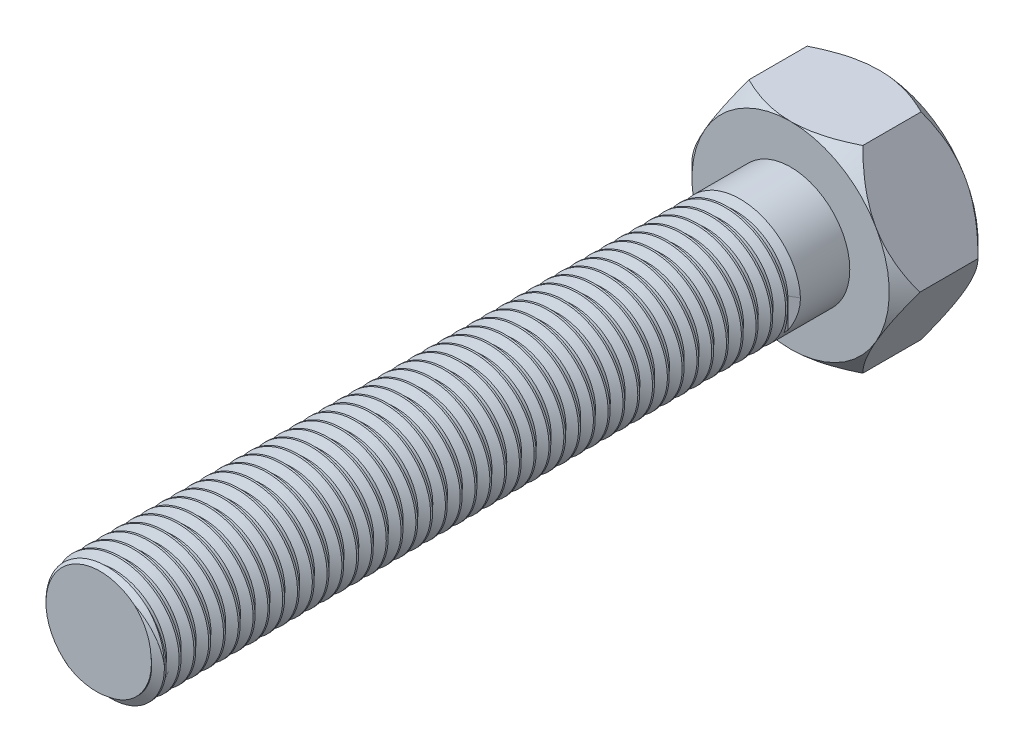
SolidWorks part; units mm, degrees
ref_plane "Front Plane" through (0, 0, 0) normal (0, 0, 1) x (1, 0, 0)
ref_plane "Top Plane" through (0, 0, 0) normal (0, 1, 0) x (1, 0, 0)
ref_plane "Right Plane" through (0, 0, 0) normal (1, 0, 0) x (0, 0, -1)
sketch "Sketch1" plane through (0, 0, 0) normal (0, 0, 1) x (1, 0, 0)
  line L1 (11.547, 0) -> (5.7735, 10)
  line L2 (5.7735, 10) -> (-5.7735, 10)
  line L3 (-5.7735, 10) -> (-11.547, 0)
  line L4 (-11.547, 0) -> (-5.7735, -10)
  line L5 (-5.7735, -10) -> (5.7735, -10)
  line L6 (5.7735, -10) -> (11.547, 0)
  circle A0 centre (0, 0) radius 10 construction
  dimension "D1" = 20
extrude "Boss-Extrude2" add sketch "Sketch1" along normal mid plane 9
sketch "Sketch5" plane through (0, 0, 4.5) normal (0, 0, 1) x (1, 0, 0)
  line L0 (-5.7735, 10) -> (-11.547, 0) construction
  circle A0 centre (0, 0) radius 10
extrude "Cut-Extrude5" cut sketch "Sketch5" against normal through all draft 45 flip side to cut
mirror "Mirror1" about plane through (0, 0, 0) normal (0, 0, 1) of "Cut-Extrude5"
sketch "Sketch6" plane through (0, 0, 4.5) normal (0, 0, 1) x (1, 0, 0)
  circle A0 centre (0, 0) radius 6
extrude "Boss-Extrude4" add sketch "Sketch6" along normal blind 70
chamfer "Chamfer1" distance 0.5 angle 45 1 edges at (6, 0, 74.5)
thread "Thread1" pitch 1.5 method cut profile "Thread Profile1" start angle 0, offset 5, length 0, pitch 1.5, diameter 12
ref_plane "Plane1" through (6, 0, 9.5) normal (0, -1, 0) x (1, 0, 0)
sketch "Thread Profile1" plane through (6, 0, 9.5) normal (0, -1, 0) x (1, 0, 0)
  line L0 (0, 0) -> (0, 1.5) construction
  line L11 (0, 0) -> (0, 1.3125)
  line L12 (0, 1.3125) -> (-0.8119, 0.8437)
  line L13 (-0.8119, 0.8437) -> (-0.8119, 0.4687)
  line L15 (-0.8119, 0.4687) -> (0, 0)
  line L17 (-0.8119, 0.6562) -> (0, 0.6562) construction
  point P2 (0, 0)
  dimension "Pitch" = 1.5
  dimension "Profile_Angle" = 60
  dimension "Profile_Land" = 0.375
  dimension "Profile_Height" = 0.8119
sketch "Sketch11" plane through (0, 0, 0) normal (0, 1, 0) x (1, 0, 0)
  line L4 (6, -9.5) -> (5.1881, -9.9687)
  line L5 (5.1881, -9.9687) -> (5.1881, -10.3437)
  line L6 (5.1881, -10.3437) -> (6, -10.8125)
  line L7 (6, -10.8125) -> (6, -9.5)
  line L8 (6, -9.5) -> (5.1881, -9.9687)
  line L9 (5.1881, -9.9687) -> (5.1881, -10.3437)
  line L10 (5.1881, -10.3437) -> (6, -10.8125)
  line L11 (6, -10.8125) -> (6, -9.5)
  dimension "D1" = 0
extrude "Cut-Extrude6" cut sketch "Sketch11" against normal through all
